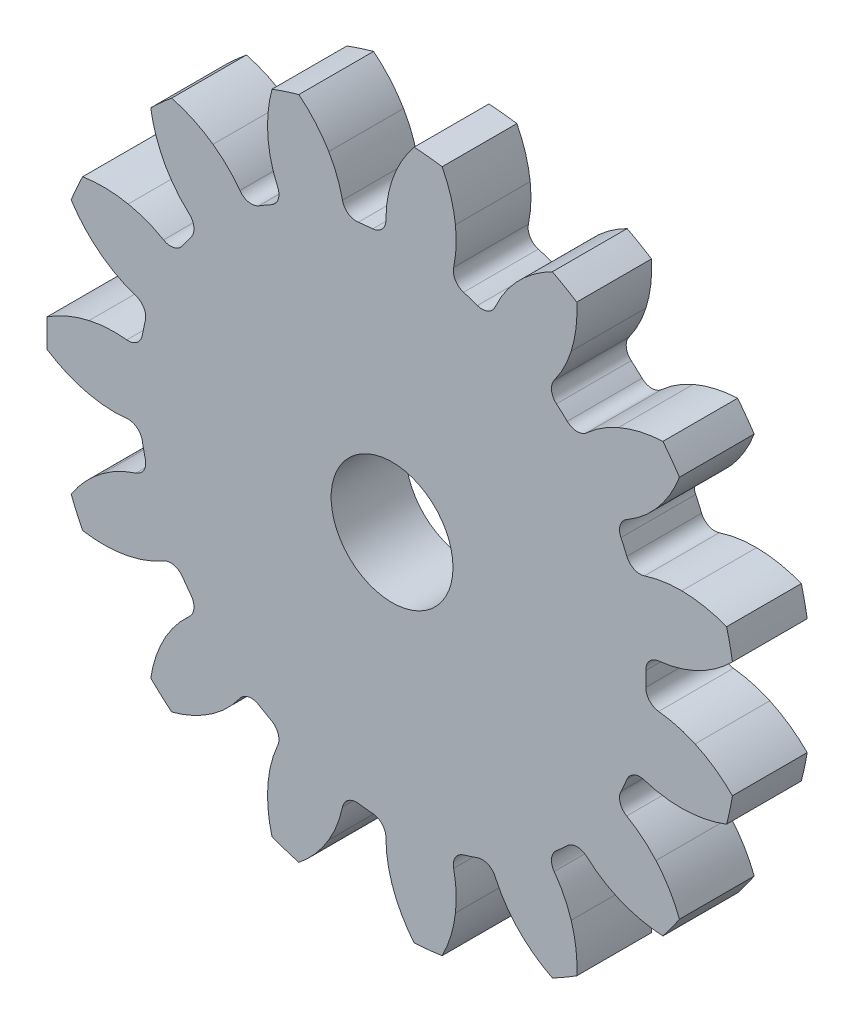
SolidWorks part; units mm, degrees
ref_plane "Front Plane" through (0, 0, 0) normal (0, 0, 1) x (1, 0, 0)
ref_plane "Top Plane" through (0, 0, 0) normal (0, 1, 0) x (1, 0, 0)
ref_plane "Right Plane" through (0, 0, 0) normal (1, 0, 0) x (0, 0, -1)
sketch "Sketch1" plane through (0, 0, 0) normal (0, 0, 1) x (1, 0, 0)
  line L0 (0, 0) -> (23.8125, 0) construction
  line L1 (23.8125, 0) -> (26.9875, 0) construction
  circle A0 centre (0, 0) radius 26.9875
  circle A1 centre (0, 0) radius 23.8125 construction
  dimension "D2" = 47.625
  dimension "D1" = 3.175
extrude "GEAR_BASE" add sketch "Sketch1" along normal mid plane 5.842
sketch "Sketch2" plane through (0, 0, 2.921) normal (0, 0, 1) x (1, 0, 0)
  line L0 (0, 0) -> (19.8438, 0) construction
  line L1 (19.8438, 0) -> (23.8125, 0) construction
  line L2 (0, 0) -> (-26.9875, 0) construction
  line L3 (0, 0) -> (-23.6815, -2.494) construction
  line L4 (-23.6815, -2.494) -> (-25.0117, 10.1362) construction
  line L5 (0, 0) -> (-24.6543, -10.9768) construction
  line L6 (-23.6815, -2.494) -> (-19.6587, -2.704) construction
  line L7 (-22.6485, -7.3538) -> (-19.0589, -5.5257) construction
  line L8 (0, 0) -> (-22.6485, -7.3538) construction
  line L9 (-23.6815, -2.494) -> (-26.965, -1.101) construction
  line L10 (-22.6485, -7.3538) -> (-25.0816, -9.9619) construction
  line L11 (-22.6485, -7.3538) -> (-21.6342, -9.6321) construction
  line L12 (-22.6485, -7.3538) -> (-18.7265, -19.433) construction
  line L13 (-23.6815, -2.494) -> (-23.6815, 0) construction
  circle A0 centre (0, 0) radius 23.8125 construction
  circle A1 centre (0, 0) radius 19.8438 construction
  circle A2 centre (0, 0) radius 26.9875 construction
  arc A3 (-25.0816, -9.9619) -> (-26.965, -1.101) centre (0, 0) cw
  arc A4 (-19.5205, -3.5671) -> (-20.733, -2.662) centre (-20.6137, -3.7669) ccw
  arc A5 (-20.0233, -6.001) -> (-19.2837, -4.681) centre (-20.3636, -4.9431) ccw
  arc A6 (-19.2837, -4.681) -> (-19.5205, -3.5671) centre (0, 0) cw
  arc A7 (-25.0816, -9.9619) -> (-22.6485, -7.3538) centre (-16.6881, -15.3532) cw
  arc A8 (-26.965, -1.101) -> (-23.6815, -2.494) centre (-21.4901, 7.2382) ccw
  arc A9 (-22.6485, -7.3538) -> (-20.0233, -6.001) centre (-17.2621, -14.5829) cw
  arc A10 (-23.6815, -2.494) -> (-20.733, -2.662) centre (-21.7011, 6.301) ccw
  dimension "D1" = 47.625
  dimension "D11" = 1.1112
  dimension "D12" = 9.9758
  dimension "D2" = 3.9688
  dimension "D3" = 24
  dimension "D5" = 9
  dimension "D7" = 9
  dimension "D8" = 4.9684
  dimension "D9" = 20
  dimension "D10" = 20
  dimension "D6" = 2.494
  dimension "D4" = 2.494
extrude "GEAR_CUT" cut sketch "Sketch2" against normal through all
ref_axis "GEAR_AXIS" through (0, 0, -3.2131) along (0, 0, 1)
pattern_circular "GEAR_TEETH" count 15 over 360 about axis through (0, 0, -3.2131) along (0, 0, 1) of "GEAR_CUT"
sketch "Sketch3" plane through (0, 0, 2.921) normal (0, 0, 1) x (1, 0, 0)
  circle A0 centre (0, 0) radius 4.7625
  dimension "D1" = 9.525
extrude "BORE" cut sketch "Sketch3" against normal through all
equation "\"N_teeth\" = 15"
equation "\"pitch_diameter\"= \"N_teeth\" / \"Pitch\""
equation "\"Pitch\"= 8"
equation "\"addendum\"=1.000/\"Pitch\""
equation "\"face_width\"=0.23"
equation "\"deddendum\"=1.250/\"Pitch\""
equation "\"tooth_thickness\"=1.571/\"Pitch\""
equation "\"Pressure_Angle\"=20.000000"
equation "\"base_fillet\"=0.35/\"Pitch\""
equation "\"D1@Sketch1\"=\"addendum\""
equation "\"D2@Sketch1\"=\"pitch_diameter\""
equation "\"D1@GEAR_BASE\" = \"face_width\""
equation "\"D1@Sketch2\"= \"pitch_diameter\""
equation "\"D2@Sketch2\"=\"deddendum\""
equation "\"D4@Sketch2\"=\"tooth_thickness\"/2"
equation "\"D6@Sketch2\"=\"tooth_thickness\"/2"
equation "\"D9@Sketch2\"=\"Pressure_Angle\""
equation "\"D10@Sketch2\"=\"Pressure_Angle\""
equation "\"D11@Sketch2\"=\"base_fillet\""
equation "\"D12@Sketch2\"=2*\"tooth_thickness\""
equation "\"D3@Sketch2\" = 360 / \"N_teeth\""
equation "\"D1@GEAR_TEETH\" = \"N_teeth\""
